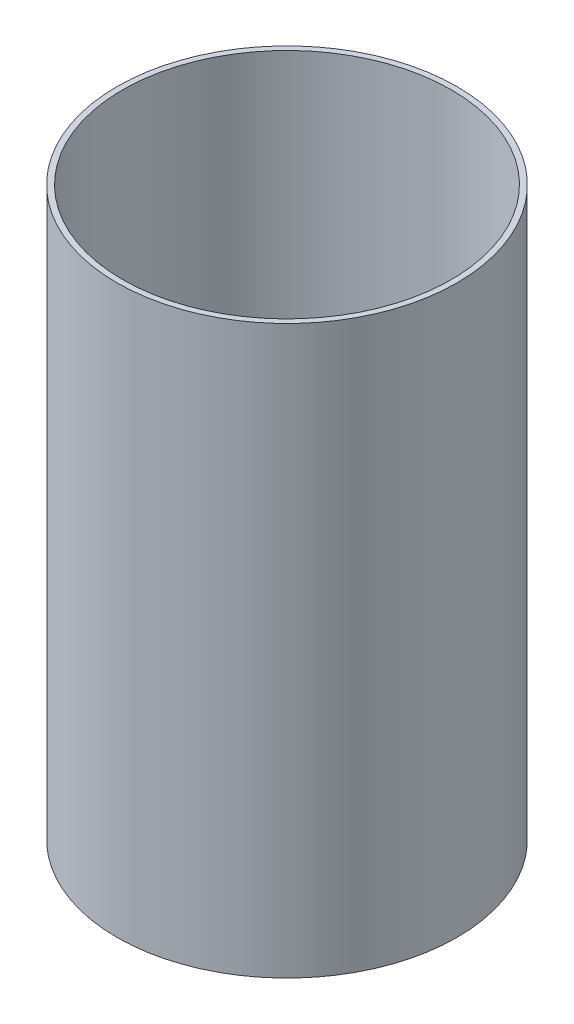
SolidWorks part; units mm, degrees
ref_plane "Front Plane" through (0, 0, 0) normal (0, 0, 1) x (1, 0, 0)
ref_plane "Top Plane" through (0, 0, 0) normal (0, 1, 0) x (1, 0, 0)
ref_plane "Right Plane" through (0, 0, 0) normal (1, 0, 0) x (0, 0, -1)
sketch "Sketch1" plane through (0, 0, 0) normal (0, 1, 0) x (1, 0, 0)
  circle A0 centre (0, 0) radius 76.1746
  circle A1 centre (0, 0) radius 73.66
  dimension "D1" = 152.3492
  dimension "D2" = 147.32
extrude "Boss-Extrude1" add sketch "Sketch1" along normal blind 254
equation "\"Mid_Coupler_Length\" = 10in"
equation "\"D1@Boss-Extrude1\"=\"Mid_Coupler_Length\""
